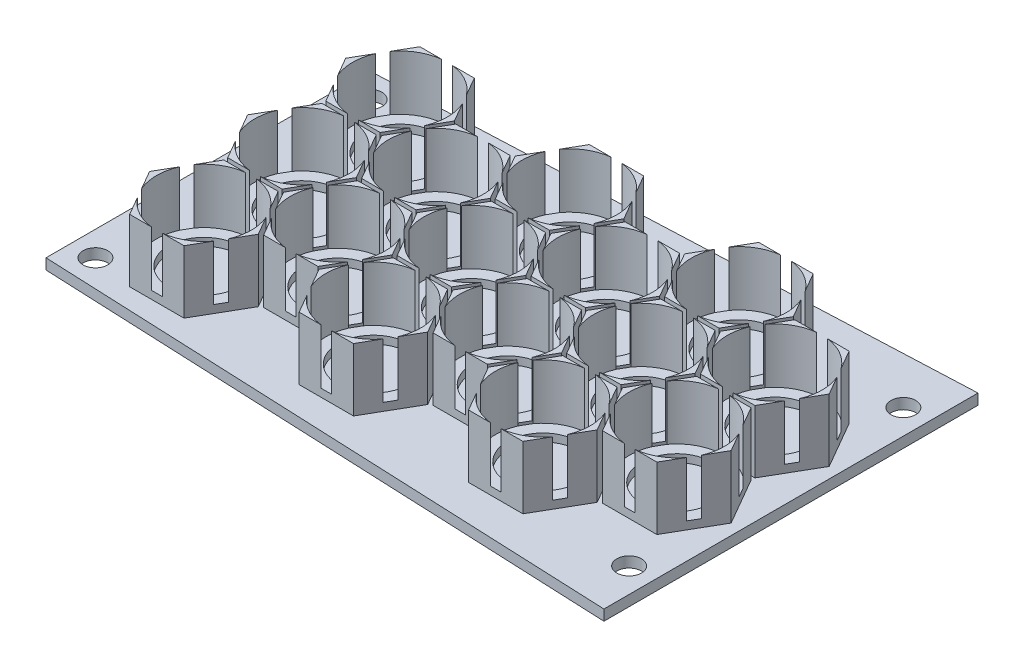
SolidWorks part; units mm, degrees
ref_plane "Front Plane" through (0, 0, 0) normal (0, 0, 1) x (1, 0, 0)
ref_plane "Top Plane" through (0, 0, 0) normal (0, 1, 0) x (1, 0, 0)
ref_plane "Right Plane" through (0, 0, 0) normal (1, 0, 0) x (0, 0, -1)
sketch "Sketch1" plane through (0, 0, 0) normal (0, 1, 0) x (1, 0, 0)
  line L0 (-118, 0) -> (118, 0)
  line L1 (-118, -65.5) -> (-118, 65.5)
  line L2 (118, -75.7) -> (118, 75.7)
  line L3 (-118, 65.5) -> (118, 75.7)
  line L4 (118, -75.7) -> (-118, -65.5)
  point P4 (0, 0)
  point P8 (-118, 0)
  point P11 (118, 0)
  dimension "D1" = 236
  dimension "D2" = 151.4
  dimension "D3" = 131
extrude "Boss-Extrude1" add sketch "Sketch1" along normal mid plane 4.3 contours L4 L2 L0 L1 | L3 L1 L0 L2 region at (2.8414, 0, -35.3614) region at (2.8414, 0, 35.3614)
sketch "Sketch3" plane through (0, 2.15, 0) normal (0, 1, 0) x (1, 0, 0)
  line L1 (-68.9015, 58.7375) -> (-90.8985, 58.7375)
  line L2 (-90.8985, 58.7375) -> (-101.897, 39.6875)
  line L3 (-101.897, 39.6875) -> (-90.8985, 20.6375)
  line L4 (-90.8985, 20.6375) -> (-68.9015, 20.6375)
  line L5 (-68.9015, 20.6375) -> (-57.903, 39.6875)
  line L6 (-57.903, 39.6875) -> (-68.9015, 58.7375)
  line L7 (-68.9015, 19.05) -> (-90.8985, 19.05)
  line L8 (-90.8985, 19.05) -> (-101.897, 0)
  line L9 (-101.897, 0) -> (-90.8985, -19.05)
  line L10 (-90.8985, -19.05) -> (-68.9015, -19.05)
  line L11 (-68.9015, -19.05) -> (-57.903, 0)
  line L12 (-57.903, 0) -> (-68.9015, 19.05)
  line L13 (-57.903, -39.6875) -> (-68.9015, -20.6375)
  line L14 (-68.9015, -20.6375) -> (-90.8985, -20.6375)
  line L15 (-90.8985, -20.6375) -> (-101.897, -39.6875)
  line L16 (-101.897, -39.6875) -> (-90.8985, -58.7375)
  line L17 (-90.8985, -58.7375) -> (-68.9015, -58.7375)
  line L18 (-68.9015, -58.7375) -> (-57.903, -39.6875)
  line L31 (-79.9, -19.05) -> (-79.9, -20.6375) construction
  line L32 (-90.8985, -58.7375) -> (-101.897, -39.6875)
  line L33 (-57.903, -39.6875) -> (-68.9015, -58.7375)
  line L34 (-68.9015, -20.6375) -> (-57.903, -39.6875)
  line L35 (-101.897, -39.6875) -> (-90.8985, -20.6375)
  line L36 (-101.897, 0) -> (-90.8985, 19.05)
  line L37 (-90.8985, -19.05) -> (-101.897, 0)
  line L38 (-57.903, 0) -> (-68.9015, -19.05)
  line L39 (-68.9015, 19.05) -> (-57.903, 0)
  line L40 (-101.897, 39.6875) -> (-90.8985, 58.7375)
  line L41 (-90.8985, 20.6375) -> (-101.897, 39.6875)
  line L42 (-57.903, 39.6875) -> (-68.9015, 20.6375)
  line L43 (-68.9015, 58.7375) -> (-57.903, 39.6875)
  line L44 (-90.8985, 58.7375) -> (-101.897, 39.6875)
  line L45 (-101.897, 39.6875) -> (-90.8985, 20.6375)
  line L46 (-68.9015, 20.6375) -> (-57.903, 39.6875)
  line L47 (-57.903, 39.6875) -> (-68.9015, 58.7375)
  line L48 (-90.8985, 19.05) -> (-101.897, 0)
  line L49 (-101.897, 0) -> (-90.8985, -19.05)
  line L50 (-68.9015, -19.05) -> (-57.903, 0)
  line L51 (-57.903, 0) -> (-68.9015, 19.05)
  line L52 (-57.903, -39.6875) -> (-68.9015, -20.6375)
  line L53 (-90.8985, -20.6375) -> (-101.897, -39.6875)
  line L54 (-101.897, -39.6875) -> (-90.8985, -58.7375)
  line L55 (-68.9015, -58.7375) -> (-57.903, -39.6875)
  line L56 (-90.8985, -58.7375) -> (-101.897, -39.6875)
  line L57 (-57.903, -39.6875) -> (-68.9015, -58.7375)
  line L58 (-68.9015, -20.6375) -> (-57.903, -39.6875)
  line L59 (-101.897, -39.6875) -> (-90.8985, -20.6375)
  line L60 (-101.897, 0) -> (-90.8985, 19.05)
  line L61 (-90.8985, -19.05) -> (-101.897, 0)
  line L62 (-57.903, 0) -> (-68.9015, -19.05)
  line L63 (-68.9015, 19.05) -> (-57.903, 0)
  line L64 (-101.897, 39.6875) -> (-90.8985, 58.7375)
  line L65 (-90.8985, 20.6375) -> (-101.897, 39.6875)
  line L66 (-57.903, 39.6875) -> (-68.9015, 20.6375)
  line L67 (-68.9015, 58.7375) -> (-57.903, 39.6875)
  line L68 (-90.8985, 58.7375) -> (-101.897, 39.6875)
  line L69 (-101.897, 39.6875) -> (-90.8985, 20.6375)
  line L70 (-68.9015, 20.6375) -> (-57.903, 39.6875)
  line L71 (-57.903, 39.6875) -> (-68.9015, 58.7375)
  line L72 (-90.8985, 19.05) -> (-101.897, 0)
  line L73 (-101.897, 0) -> (-90.8985, -19.05)
  line L74 (-68.9015, -19.05) -> (-57.903, 0)
  line L75 (-57.903, 0) -> (-68.9015, 19.05)
  line L76 (-57.903, -39.6875) -> (-68.9015, -20.6375)
  line L77 (-90.8985, -20.6375) -> (-101.897, -39.6875)
  line L78 (-101.897, -39.6875) -> (-90.8985, -58.7375)
  line L79 (-68.9015, -58.7375) -> (-57.903, -39.6875)
  line L80 (-90.8985, -58.7375) -> (-101.897, -39.6875)
  line L81 (-57.903, -39.6875) -> (-68.9015, -58.7375)
  line L82 (-68.9015, -20.6375) -> (-57.903, -39.6875)
  line L83 (-101.897, -39.6875) -> (-90.8985, -20.6375)
  line L84 (-101.897, 0) -> (-90.8985, 19.05)
  line L85 (-90.8985, -19.05) -> (-101.897, 0)
  line L86 (-57.903, 0) -> (-68.9015, -19.05)
  line L87 (-68.9015, 19.05) -> (-57.903, 0)
  line L88 (-101.897, 39.6875) -> (-90.8985, 58.7375)
  line L89 (-90.8985, 20.6375) -> (-101.897, 39.6875)
  line L90 (-57.903, 39.6875) -> (-68.9015, 20.6375)
  line L91 (-68.9015, 58.7375) -> (-57.903, 39.6875)
  line L92 (-90.8985, 58.7375) -> (-101.897, 39.6875)
  line L93 (-101.897, 39.6875) -> (-90.8985, 20.6375)
  line L94 (-68.9015, 20.6375) -> (-57.903, 39.6875)
  line L95 (-57.903, 39.6875) -> (-68.9015, 58.7375)
  line L96 (-90.8985, 19.05) -> (-101.897, 0)
  line L97 (-101.897, 0) -> (-90.8985, -19.05)
  line L98 (-68.9015, -19.05) -> (-57.903, 0)
  line L99 (-57.903, 0) -> (-68.9015, 19.05)
  line L100 (-57.903, -39.6875) -> (-68.9015, -20.6375)
  line L101 (-90.8985, -20.6375) -> (-101.897, -39.6875)
  line L102 (-101.897, -39.6875) -> (-90.8985, -58.7375)
  line L103 (-68.9015, -58.7375) -> (-57.903, -39.6875)
  line L104 (-90.8985, -58.7375) -> (-101.897, -39.6875)
  line L105 (-57.903, -39.6875) -> (-68.9015, -58.7375)
  line L106 (-68.9015, -20.6375) -> (-57.903, -39.6875)
  line L107 (-101.897, -39.6875) -> (-90.8985, -20.6375)
  line L108 (-101.897, 0) -> (-90.8985, 19.05)
  line L109 (-90.8985, -19.05) -> (-101.897, 0)
  line L110 (-57.903, 0) -> (-68.9015, -19.05)
  line L111 (-68.9015, 19.05) -> (-57.903, 0)
  line L112 (-101.897, 39.6875) -> (-90.8985, 58.7375)
  line L113 (-90.8985, 20.6375) -> (-101.897, 39.6875)
  line L114 (-57.903, 39.6875) -> (-68.9015, 20.6375)
  line L115 (-68.9015, 58.7375) -> (-57.903, 39.6875)
  line L135 (-79.9, 20.6375) -> (-79.9, 19.05) construction
  line L136 (-63.4022, -9.525) -> (-62.0274, -10.3188) construction
  line L138 (0, 0) -> (-118, 0) construction
  line L139 (-118, -65.5) -> (-118, 65.5) construction
  line L140 (-34.5311, 38.8938) -> (-23.5326, 19.8438)
  line L141 (-23.5326, -19.8438) -> (-34.5311, -0.7938)
  line L142 (-34.5311, -0.7938) -> (-56.5281, -0.7938)
  line L143 (-56.5281, -0.7938) -> (-67.5267, -19.8438)
  line L144 (-67.5267, -19.8438) -> (-56.5281, -38.8938)
  line L145 (-56.5281, -38.8938) -> (-34.5311, -38.8938)
  line L146 (-34.5311, -38.8938) -> (-23.5326, -19.8438)
  line L147 (-56.5281, 38.8938) -> (-34.5311, 38.8938)
  line L148 (-67.5267, 19.8438) -> (-56.5281, 38.8938)
  line L149 (-56.5281, 0.7938) -> (-67.5267, 19.8438)
  line L150 (-34.5311, 0.7938) -> (-56.5281, 0.7938)
  line L151 (-23.5326, 19.8438) -> (-34.5311, 0.7938)
  circle A0 centre (-79.9, 39.6875) radius 19.05 construction
  circle A1 centre (-79.9, 0) radius 19.05 construction
  circle A2 centre (-79.9, -39.6875) radius 19.05 construction
  circle A3 centre (-45.5296, -19.8438) radius 19.05 construction
  dimension "D1" = 38.1
  dimension "D3" = 38.1
  dimension "D2" = 1.5875
extrude "Boss-Extrude2" add sketch "Sketch3" along normal blind 25.4 contours L5 L6 L1 L2 L3 L4 | L151 L140 L147 L148 L149 L150 | L11 L12 L7 L8 L9 L10 | L17 L18 L13 L14 L15 L16 | L145 L146 L141 L142 L143 L144 region at (-79.9, 2.15, -39.6875) region at (-79.9, 2.15, 0) region at (-79.9, 2.15, 39.6875) region at (-45.5296, 2.15, -19.8438) region at (-45.5296, 2.15, 19.8438)
sketch "Sketch4" plane through (0, 27.55, 0) normal (0, 1, 0) x (1, 0, 0)
  line L0 (-101.897, 0) -> (-57.903, 0) construction
  line L2 (-101.897, -39.6875) -> (-57.903, -39.6875) construction
  line L3 (-67.5267, 19.8438) -> (-23.5326, 19.8438) construction
  circle A0 centre (-79.9, 0) radius 14.351
  circle A1 centre (-79.9, 0) radius 19.177
  circle A2 centre (-79.9, -39.6875) radius 14.351
  circle A3 centre (-79.9, -39.6875) radius 19.177
  circle A4 centre (-79.9, 39.6875) radius 14.351
  circle A5 centre (-79.9, 39.6875) radius 19.177
  circle A6 centre (-45.5296, 19.8438) radius 14.351
  circle A7 centre (-45.5296, 19.8438) radius 19.177
  circle A8 centre (-45.5296, -19.8438) radius 19.177
  circle A9 centre (-45.5296, -19.8438) radius 14.351
  dimension "D1" = 28.702
  dimension "D2" = 38.354
extrude "Cut-Extrude1" cut sketch "Sketch4" against normal blind 25.4 contours A2 | A0 | A9 | A6 | A4
extrude "Cut-Extrude2" cut sketch "Sketch4<4>" against normal blind 22.225 contours A3 | A1 | A8 | A7 | A5
sketch "Sketch4<4>" plane through (0, 27.55, 0) normal (0, 1, 0) x (1, 0, 0) same geometry as "Sketch4"
pattern_linear "LPattern1" count 3 spacing 68.58 along (1, 0, 0) of "Boss-Extrude2", "Cut-Extrude1", "Cut-Extrude2"
sketch "Sketch5" plane through (0, 2.15, 0) normal (0, 1, 0) x (1, 0, 0)
  line L0 (91.6304, -38.8938) -> (91.6304, -40.5096) construction
  line L1 (93.8338, -38.8938) -> (89.427, -38.8938) construction
  line L3 (113.6274, -59.5596) -> (102.6289, -40.5096)
  line L4 (102.6289, -40.5096) -> (80.6319, -40.5096)
  line L5 (80.6319, -40.5096) -> (69.6333, -59.5596)
  line L6 (69.6333, -59.5596) -> (80.6319, -78.6096)
  line L7 (80.6319, -78.6096) -> (102.6289, -78.6096)
  line L8 (102.6289, -78.6096) -> (113.6274, -59.5596)
  circle A0 centre (91.6304, -59.5596) radius 19.05 construction
  dimension "D2" = 38.1
  dimension "D1" = 1.6158
sketch "Sketch6" plane through (0, 2.15, 0) normal (0, 1, 0) x (1, 0, 0)
  line L0 (-118, -65.5) -> (-118, -55.5) construction
  line L1 (-118, -65.5) -> (-118, 65.5) construction
  line L2 (-118, -55.5) -> (-108, -55.5) construction
  line L3 (-118, 65.5) -> (-118, 55.5) construction
  line L4 (-118, 55.5) -> (-108, 55.5) construction
  line L5 (0, 0) -> (0, 5.143) construction
  circle A0 centre (-108, -55.5) radius 5
  circle A1 centre (-108, 55.5) radius 5
  circle A2 centre (108, -55.5) radius 5
  circle A3 centre (108, 55.5) radius 5
  dimension "D3" = 10
  dimension "D6" = 10
  dimension "D1" = 10
  dimension "D2" = 10
  dimension "D4" = 10
  dimension "D5" = 10
extrude "Cut-Extrude3" cut sketch "Sketch6" against normal through all
